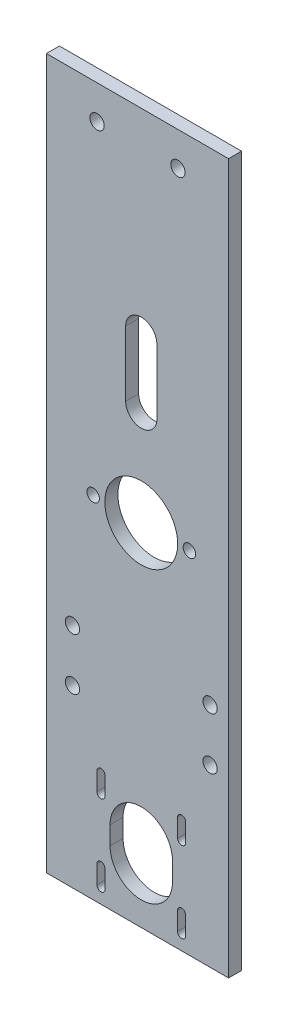
SolidWorks part; units mm, degrees
ref_plane "Front Plane" through (0, 0, 0) normal (0, 0, 1) x (1, 0, 0)
ref_plane "Top Plane" through (0, 0, 0) normal (0, 1, 0) x (1, 0, 0)
ref_plane "Right Plane" through (0, 0, 0) normal (1, 0, 0) x (0, 0, -1)
sketch "Sketch1" plane through (0, 0, 0) normal (0, 0, 1) x (1, 0, 0)
  line L0 (-26.4505, -10) -> (26.4505, 10) construction
  line L2 (-36.4505, -77.3566) -> (-36.4505, 77.3566)
  line L3 (-36.4505, 77.3566) -> (33.5495, 77.3566)
  line L4 (33.5495, -77.3566) -> (33.5495, 77.3566)
  line L5 (-26.4505, 10) -> (26.4505, -10) construction
  line L6 (-36.4505, -77.3566) -> (33.5495, -77.3566)
  line L7 (-18.5, 57.3566) -> (18.5, 57.3566) construction
  line L8 (-15.5, -33.6434) -> (-15.5, -40.6434) construction
  line L9 (-15.5, -68.1434) -> (15.5, -68.1434) construction
  line L11 (-15.5, -68.1434) -> (-15.5, -37.1434) construction
  line L14 (-15.5, -37.1434) -> (15.5, -37.1434) construction
  line L15 (15.5, -68.1434) -> (15.5, -37.1434) construction
  line L16 (-15.5, -68.1434) -> (15.5, -37.1434) construction
  line L17 (-15.5, -37.1434) -> (15.5, -68.1434) construction
  line L18 (-13.95, -33.6434) -> (-13.95, -40.6434)
  line L19 (-17.05, -33.6434) -> (-17.05, -40.6434)
  line L20 (15.5, -33.6434) -> (15.5, -40.6434) construction
  line L21 (17.05, -33.6434) -> (17.05, -40.6434)
  line L22 (13.95, -33.6434) -> (13.95, -40.6434)
  line L23 (15.5, -64.6434) -> (15.5, -71.6434) construction
  line L24 (17.05, -64.6434) -> (17.05, -71.6434)
  line L25 (13.95, -64.6434) -> (13.95, -71.6434)
  line L26 (-15.5, -64.6434) -> (-15.5, -71.6434) construction
  line L27 (-13.95, -64.6434) -> (-13.95, -71.6434)
  line L28 (-17.05, -64.6434) -> (-17.05, -71.6434)
  line L29 (0, -56.1434) -> (0, -49.1434) construction
  line L30 (-12, -56.1434) -> (-12, -49.1434)
  line L31 (12, -56.1434) -> (12, -49.1434)
  line L33 (-36.4505, 77.3566) -> (33.5495, 77.3566)
  line L34 (-36.4505, 77.3566) -> (-36.4505, 195.3566)
  line L35 (-36.4505, 195.3566) -> (33.5495, 195.3566)
  line L36 (33.5495, 77.3566) -> (33.5495, 195.3566)
  line L38 (0, 119.8566) -> (0, 94.8566) construction
  line L39 (6, 119.8566) -> (6, 94.8566)
  line L40 (-6, 119.8566) -> (-6, 94.8566)
  circle A0 centre (-18.5, 57.3566) radius 2.4
  circle A1 centre (18.5, 57.3566) radius 2.4
  circle A2 centre (0, 57.3566) radius 5
  circle A3 centre (-26.4505, 10) radius 2.75
  circle A4 centre (26.4505, 10) radius 2.75
  circle A5 centre (26.4505, -10) radius 2.75
  circle A6 centre (-26.4505, -10) radius 2.75
  circle A7 centre (0, 57.3566) radius 14
  arc A13 (-13.95, -33.6434) -> (-17.05, -33.6434) centre (-15.5, -33.6434) ccw
  arc A14 (-17.05, -40.6434) -> (-13.95, -40.6434) centre (-15.5, -40.6434) ccw
  arc A15 (17.05, -33.6434) -> (13.95, -33.6434) centre (15.5, -33.6434) ccw
  arc A16 (13.95, -40.6434) -> (17.05, -40.6434) centre (15.5, -40.6434) ccw
  arc A17 (17.05, -64.6434) -> (13.95, -64.6434) centre (15.5, -64.6434) ccw
  arc A18 (13.95, -71.6434) -> (17.05, -71.6434) centre (15.5, -71.6434) ccw
  arc A19 (-13.95, -64.6434) -> (-17.05, -64.6434) centre (-15.5, -64.6434) ccw
  arc A20 (-17.05, -71.6434) -> (-13.95, -71.6434) centre (-15.5, -71.6434) ccw
  arc A21 (-12, -56.1434) -> (12, -56.1434) centre (0, -56.1434) ccw
  arc A22 (12, -49.1434) -> (-12, -49.1434) centre (0, -49.1434) ccw
  arc A23 (6, 119.8566) -> (-6, 119.8566) centre (0, 119.8566) ccw
  arc A24 (-6, 94.8566) -> (6, 94.8566) centre (0, 94.8566) ccw
  circle A25 centre (14.0909, 182.3877) radius 2.75
  circle A26 centre (-16.9918, 182.3877) radius 2.75
  point P0 (0, 0)
  point P5 (-36.4505, 0)
  point P6 (0, -52.6434)
  point P25 (-15.5, -37.1434)
  point P38 (15.5, -37.1434)
  point P45 (15.5, -68.1434)
  point P52 (-15.5, -68.1434)
  point P57 (0, -52.6434)
  point P64 (0, 107.3566)
  point P67 (0, 107.3566)
  point P75 (0, 0)
  dimension "D4" = 4.8
  dimension "D5" = 10
  dimension "D6" = 5.5
  dimension "D11" = 28
  dimension "D7" = 12
  dimension "D12" = 1.55
  dimension "D17" = 6
  dimension "D20" = 5.5
  dimension "D1" = 70
  dimension "D2" = 31
  dimension "D3" = 37
  dimension "D8" = 20
  dimension "D9" = 7
  dimension "D10" = 20
  dimension "D13" = 110
  dimension "D14" = 7
  dimension "D15" = 50
  dimension "D16" = 138
  dimension "D18" = 25
  dimension "D19" = 12.9688
extrude "Boss-Extrude1" add sketch "Sketch1" along normal blind 5 contours L2 L6 L4 L3 A7 A6 A5 A4 A3 A1 A0 region at (-1.6809, 0.1525, 0)
extrude "Boss-Extrude2" add sketch "Sketch1<4>" along normal blind 5 contours L3 L36 L35 L34 A24 L40 A23 L39 region at (-1.5273, 137.6121, 0)
sketch "Sketch1<4>" plane through (0, 0, 0) normal (0, 0, 1) x (1, 0, 0) same geometry as "Sketch1"
